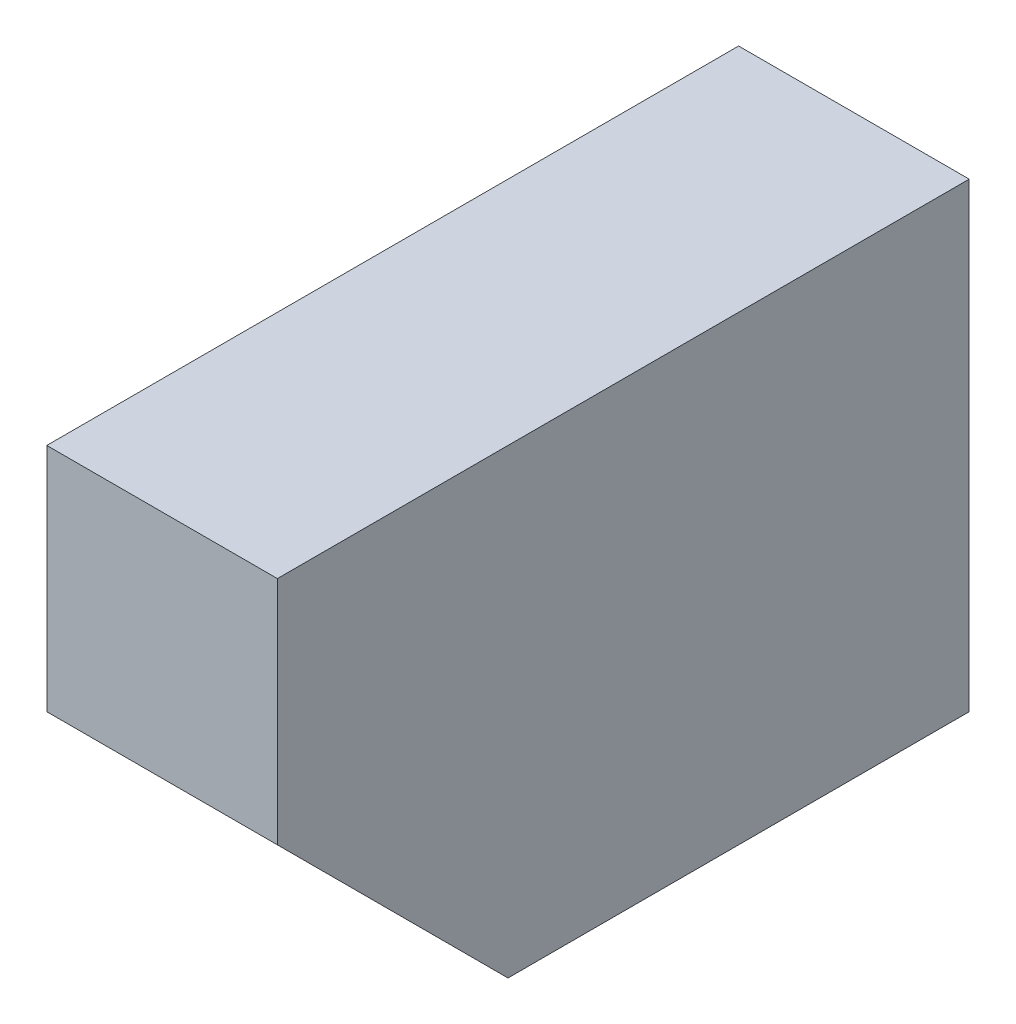
SolidWorks part; units mm, degrees
ref_plane "Front Plane" through (0, 0, 0) normal (0, 0, 1) x (1, 0, 0)
ref_plane "Top Plane" through (0, 0, 0) normal (0, 1, 0) x (1, 0, 0)
ref_plane "Right Plane" through (0, 0, 0) normal (1, 0, 0) x (0, 0, -1)
sketch "Sketch2" plane through (0, 0, 0) normal (0, 0, 1) x (1, 0, 0)
  line L1 (-25, 50) -> (25, 50)
  line L2 (-25, 50) -> (-25, -50)
  line L3 (-25, -50) -> (25, -50)
  line L4 (25, 50) -> (25, -50)
  dimension "block_length" = 50
  dimension "D1" = 25
  dimension "D2" = 50
  dimension "block_width" = 100
extrude "Boss-Extrude1" add sketch "Sketch2" along normal blind 150
sketch "Sketch3" plane through (-25, 0, 0) normal (-1, 0, 0) x (0, 0, 1)
  line L0 (150, 0) -> (100, -50)
  line L1 (150, 50) -> (150, -50) construction
  line L2 (150, -50) -> (0, -50) construction
  line L3 (150, 0) -> (150, -50)
  line L4 (150, -50) -> (100, -50)
  dimension "D1" = 45
  dimension "D2" = 50
extrude "Cut-Extrude1" cut sketch "Sketch3" against normal blind 150
ref_axis "Axis1" through (0, 0, 157.5) along (0, 0, -1)
equation "\"D1@Sketch2\" = \"block_length@Sketch2\" / 2"
equation "\"D2@Sketch2\"=\"block_width@Sketch2\"/2"
